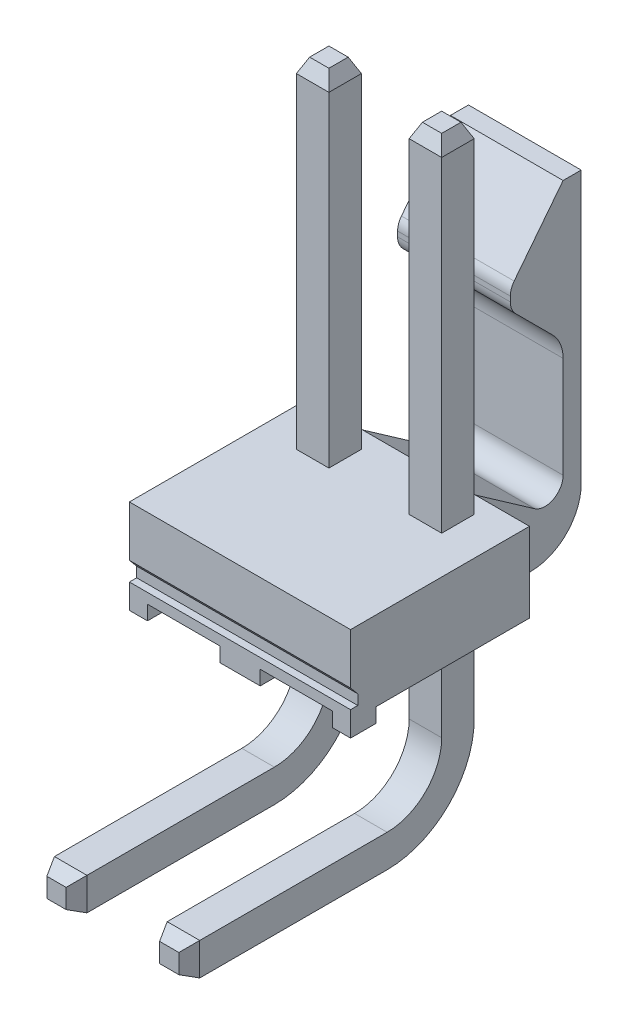
SolidWorks part; units mm, degrees
ref_plane "Front Plane" through (0, 0, 0) normal (0, 0, 1) x (1, 0, 0)
ref_plane "Top Plane" through (0, 0, 0) normal (0, 1, 0) x (1, 0, 0)
ref_plane "Right Plane" through (0, 0, 0) normal (1, 0, 0) x (0, 0, -1)
ref_plane "Plane2" through (1.98, 0, 0) normal (1, 0, 0) x (0, 0, -1)
ref_plane "Plane3" through (0, 12.83, 0) normal (0, 1, 0) x (1, 0, 0)
ref_plane "Plane4" through (0, 0, 7.11) normal (0, 0, 1) x (1, 0, 0)
sketch "Sketch17" plane through (0, 0, 0) normal (1, 0, 0) x (0, 0, -1)
  line L20 (-2.8893, -0.6837) -> (-2.8893, -1.0393)
  line L21 (-2.8893, -1.0393) -> (-3.1432, -1.0393)
  line L22 (-3.1432, -1.0393) -> (-3.1432, -1.905)
  line L23 (-3.1432, -1.905) -> (-2.2542, -1.905)
  line L24 (-2.2542, -1.905) -> (-2.2542, -1.397)
  line L25 (-2.2542, -1.397) -> (3.1432, -1.397)
  line L26 (3.1432, -1.397) -> (3.1432, 1.397) construction
  line L27 (3.1432, 1.397) -> (-3.1432, 1.397)
  line L28 (-3.1432, 1.397) -> (-3.1432, -0.381)
  line L29 (-3.1432, -0.381) -> (-2.8893, -0.6837)
  line L30 (3.1432, -1.905) -> (5.0863, -1.905) construction
  line L31 (6.8643, -0.127) -> (6.8644, 9.4234) construction
  line L32 (6.8644, 9.4234) -> (6.2294, 9.4234) construction
  line L33 (6.2294, 9.4234) -> (4.5098, 7.2224) construction
  line L34 (4.3751, 6.8315) -> (4.3751, 6.6552) construction
  line L35 (4.5611, 6.2062) -> (5.8574, 4.9099) construction
  line L36 (6.2294, 4.0119) -> (6.2294, 0.4559) construction
  line L37 (5.2301, -0.0642) -> (3.1432, 1.397) construction
  line L38 (3.1432, 1.397) -> (3.1432, -1.397)
  line L39 (3.1432, -1.397) -> (3.1432, -1.905) construction
  line L40 (-3.1432, -1000.381) -> (-3.1433, 48999.619) construction
  line L41 (0, -1000) -> (0, 49000) construction
  line L42 (3.1433, -1001.397) -> (3.1432, 48998.603) construction
  line L43 (6.2294, -999.5441) -> (6.2293, 49000.4559) construction
  line L44 (6.8644, -1000.127) -> (6.8643, 48999.873) construction
  line L45 (5.0102, -997.747) -> (5.0102, 49002.253) construction
  line L46 (-1000, 0) -> (49000, 0) construction
  line L47 (-996.8567, 1.397) -> (49003.1433, 1.397) construction
  line L48 (-996.8567, -1.397) -> (49003.1433, -1.397) construction
  line L49 (-996.8567, -1.905) -> (49003.1433, -1.905) construction
  line L50 (-993.7706, 9.4234) -> (49006.2294, 9.4234) construction
  arc A5 (5.0863, -1.905) -> (6.8643, -0.127) centre (5.0863, -0.127) ccw construction
  arc A6 (4.5098, 7.2224) -> (4.3751, 6.8315) centre (5.0101, 6.8315) ccw construction
  arc A7 (4.3751, 6.6552) -> (4.5611, 6.2062) centre (5.0101, 6.6552) ccw construction
  arc A8 (6.2294, 4.0119) -> (5.8574, 4.9099) centre (4.9594, 4.0119) ccw construction
  arc A9 (5.2301, -0.0642) -> (6.2294, 0.4559) centre (5.5943, 0.4559) ccw construction
  dimension "D15" = 1.778
  dimension "D22" = 0.635
  dimension "D26" = 0.635
  dimension "D27" = 0.635
  dimension "D32" = 1.27
  dimension "D1" = 1.397
  dimension "D2" = 1.397
  dimension "D3" = 6.2865
  dimension "D4" = 1.778
  dimension "D5" = 0.8657
  dimension "D6" = 0.508
  dimension "D7" = 0.889
  dimension "D8" = 3.1433
  dimension "D9" = 3.1432
  dimension "D10" = 40
  dimension "D11" = 2.2543
  dimension "D12" = 1.905
  dimension "D13" = 0.254
  dimension "D14" = 1.9431
  dimension "D16" = 1.778
  dimension "D17" = 3.0861
  dimension "D18" = 3.7211
  dimension "D19" = 2.4511
  dimension "D20" = 0.9411
  dimension "D21" = 35
  dimension "D23" = 9.4234
  dimension "D24" = 1.8542
  dimension "D25" = 0.1763
  dimension "D28" = 38
  dimension "D29" = 45
  dimension "D30" = 1.8161
  dimension "D31" = 5.4115
  dimension "D33" = 2.5919
  dimension "D34" = 0.635
extrude "Boss-Extrude14" add sketch "Sketch17" along normal blind 3.885 and the other way blind 3.885
sketch "Sketch18" plane through (0, 0, 0) normal (1, 0, 0) x (0, 0, -1)
  line L0 (6.2294, 9.4234) -> (4.5098, 7.2224) construction
  line L1 (6.8644, 9.4234) -> (6.2294, 9.4234) construction
  line L2 (6.8643, -0.127) -> (6.8644, 9.4234) construction
  line L3 (3.1432, -1.905) -> (5.0863, -1.905) construction
  line L5 (5.2301, -0.0642) -> (3.1432, 1.397) construction
  line L6 (4.5611, 6.2062) -> (5.8574, 4.9099) construction
  line L7 (6.2294, 4.0119) -> (6.2294, 0.4559) construction
  line L8 (4.3752, 6.8315) -> (4.3751, 6.6552) construction
  line L9 (6.2294, 9.4234) -> (4.5098, 7.2224)
  line L10 (6.8644, 9.4234) -> (6.2294, 9.4234)
  line L11 (6.8643, -0.127) -> (6.8644, 9.4234)
  line L12 (3.1432, -1.905) -> (5.0863, -1.905)
  line L13 (3.1432, 1.397) -> (3.1432, -1.905)
  line L14 (5.2301, -0.0642) -> (3.1432, 1.397)
  line L15 (4.5611, 6.2062) -> (5.8574, 4.9099)
  line L16 (6.2294, 4.0119) -> (6.2294, 0.4559)
  line L17 (4.3752, 6.8315) -> (4.3751, 6.6552)
  arc A0 (5.0863, -1.905) -> (6.8643, -0.127) centre (5.0863, -0.127) ccw construction
  arc A1 (5.2301, -0.0642) -> (6.2294, 0.4559) centre (5.5943, 0.4559) ccw construction
  arc A2 (6.2294, 4.0119) -> (5.8574, 4.9099) centre (4.9594, 4.0119) ccw construction
  arc A3 (4.3751, 6.6552) -> (4.5611, 6.2062) centre (5.0101, 6.6552) ccw construction
  arc A4 (4.5098, 7.2224) -> (4.3752, 6.8315) centre (5.0101, 6.8315) ccw construction
  arc A5 (5.0863, -1.905) -> (6.8643, -0.127) centre (5.0863, -0.127) ccw
  arc A6 (5.2301, -0.0642) -> (6.2294, 0.4559) centre (5.5943, 0.4559) ccw
  arc A7 (6.2294, 4.0119) -> (5.8574, 4.9099) centre (4.9594, 4.0119) ccw
  arc A8 (4.3751, 6.6552) -> (4.5611, 6.2062) centre (5.0101, 6.6552) ccw
  arc A9 (4.5098, 7.2224) -> (4.3752, 6.8315) centre (5.0101, 6.8315) ccw
extrude "Boss-Extrude15" add sketch "Sketch18" along normal blind 1.98 and the other way blind 1.98
sketch "Sketch19" plane through (0, 0, 2.2542) normal (0, 0, -1) x (-1, 0, 0)
  line L0 (0, -1000) -> (0, 49000) construction
  line L1 (3.885, -1.397) -> (-3.885, -1.397) construction
  line L2 (-3.25, -1.397) -> (-0.71, -1.397)
  line L3 (-3.25, -1.397) -> (-3.25, -1.905)
  line L4 (-3.25, -1.905) -> (-0.71, -1.905)
  line L5 (-0.71, -1.397) -> (-0.71, -1.905)
  line L6 (-3.25, -1.397) -> (-0.71, -1.905) construction
  line L7 (-3.25, -1.905) -> (-0.71, -1.397) construction
  line L8 (3.885, -1.905) -> (-3.885, -1.905) construction
  line L9 (3.25, -1.397) -> (0.71, -1.397)
  line L10 (0.71, -1.397) -> (0.71, -1.905)
  line L11 (3.25, -1.905) -> (0.71, -1.905)
  line L12 (3.25, -1.397) -> (3.25, -1.905)
  point P1 (-1.98, -1.651)
  dimension "D1" = 1.42
  dimension "D2" = 2.54
extrude "Cut-Extrude4" cut sketch "Sketch19" against normal through all
sketch "Sketch20" plane through (0, 12.83, 0) normal (0, 1, 0) x (1, 0, 0)
  line L8 (-1.4097, 1.3907) -> (-1.4097, 2.5337)
  line L9 (-1.4097, 2.5337) -> (-2.5527, 2.5337)
  line L10 (-2.5527, 2.5337) -> (-2.5527, 1.3907)
  line L11 (-2.5527, 1.3907) -> (-1.4097, 1.3907)
  line L12 (2.5527, 1.3907) -> (2.5527, 2.5337)
  line L13 (2.5527, 2.5337) -> (1.4097, 2.5337)
  line L14 (1.4097, 2.5337) -> (1.4097, 1.3907)
  line L15 (1.4097, 1.3907) -> (2.5527, 1.3907)
  line L16 (0, -1000) -> (0, 49000) construction
  point P9 (1.9812, 1.9622)
  point P12 (1.4097, 1.9622)
  point P13 (1.9812, 2.5337)
  dimension "D1" = 2.8194
  dimension "D2" = 2.8194
  dimension "D3" = 1.143
  dimension "D4" = 1.143
  dimension "D5" = 1.3907
  dimension "D6" = 1.143
extrude "Cut-Extrude5" cut sketch "Sketch20" against normal through all
sketch "Sketch22" plane through (0, 0, 7.11) normal (0, 0, 1) x (1, 0, 0)
  line L0 (-998.02, -7.3152) -> (49001.98, -7.3152) construction
  line L3 (1.9812, -987.17) -> (1.9812, 49012.83) construction
  point P3 (1.9812, -7.3152)
  dimension "D1" = 7.3152
sketch "Sketch21" plane through (1.98, 0, 0) normal (1, 0, 0) x (0, 0, -1)
  line L0 (1.9622, 12.83) -> (1.9622, -4.8275)
  line L1 (4.2748, 12.83) -> (-4.2748, 12.83) construction
  line L2 (-0.5255, -7.3152) -> (-7.11, -7.3152)
  line L3 (-7.11, 4.2748) -> (-7.11, -4.2748) construction
  line L4 (1.3922, 12.83) -> (1.3922, -4.8275) construction
  line L5 (-0.5255, -6.7452) -> (-7.11, -6.7452) construction
  line L6 (2.5322, 12.83) -> (2.5322, -4.8275) construction
  line L7 (-0.5255, -7.8852) -> (-7.11, -7.8852) construction
  arc A0 (1.9622, -4.8275) -> (-0.5255, -7.3152) centre (-0.5255, -4.8275) cw
  arc A1 (1.3922, -4.8275) -> (-0.5255, -6.7452) centre (-0.5255, -4.8275) cw construction
  arc A2 (2.5322, -4.8275) -> (-0.5255, -7.8852) centre (-0.5255, -4.8275) cw construction
  dimension "D1" = 0.57
  dimension "D3" = 1.9177
  dimension "D4" = 3.0577
  dimension "D2" = 0.57
sweep "Sweep1" add profiles "Sketch20<2>" path "Sketch21"
sketch "Sketch20<2>" plane through (0, 12.83, 0) normal (0, 1, 0) x (1, 0, 0) same geometry as "Sketch20"
sketch "Sketch23" plane through (0, 12.83, 0) normal (0, 1, 0) x (1, 0, 0)
  line L4 (1.4097, 1.3907) -> (2.5527, 1.3907)
  line L5 (2.5527, 1.3907) -> (2.5527, 2.5337)
  line L6 (2.5527, 2.5337) -> (1.4097, 2.5337)
  line L7 (1.4097, 2.5337) -> (1.4097, 1.3907)
  line L8 (1.4097, 1.3907) -> (2.5527, 1.3907)
  line L9 (2.5527, 1.3907) -> (2.5527, 2.5337)
  line L10 (2.5527, 2.5337) -> (1.4097, 2.5337)
  line L11 (1.4097, 2.5337) -> (1.4097, 1.3907)
  line L12 (-2.5527, 1.3907) -> (-1.4097, 1.3907)
  line L13 (-1.4097, 1.3907) -> (-1.4097, 2.5337)
  line L14 (-1.4097, 2.5337) -> (-2.5527, 2.5337)
  line L15 (-2.5527, 2.5337) -> (-2.5527, 1.3907)
  line L16 (-2.5527, 1.3907) -> (-1.4097, 1.3907)
  line L17 (-1.4097, 1.3907) -> (-1.4097, 2.5337)
  line L18 (-1.4097, 2.5337) -> (-2.5527, 2.5337)
  line L19 (-2.5527, 2.5337) -> (-2.5527, 1.3907)
  dimension "D1" = 0
  dimension "D2" = 0
extrude "Boss-Extrude16" add sketch "Sketch23" along normal blind 0.5 draft 25
sketch "Sketch24" plane through (0, 0, 7.11) normal (0, 0, 1) x (1, 0, 0)
  line L4 (2.5527, -6.7437) -> (1.4097, -6.7437)
  line L5 (1.4097, -6.7437) -> (1.4097, -7.8867)
  line L6 (1.4097, -7.8867) -> (2.5527, -7.8867)
  line L7 (2.5527, -7.8867) -> (2.5527, -6.7437)
  line L8 (2.5527, -6.7437) -> (1.4097, -6.7437)
  line L9 (1.4097, -6.7437) -> (1.4097, -7.8867)
  line L10 (1.4097, -7.8867) -> (2.5527, -7.8867)
  line L11 (2.5527, -7.8867) -> (2.5527, -6.7437)
  line L12 (-1.4097, -6.7437) -> (-2.5527, -6.7437)
  line L13 (-2.5527, -6.7437) -> (-2.5527, -7.8867)
  line L14 (-2.5527, -7.8867) -> (-1.4097, -7.8867)
  line L15 (-1.4097, -7.8867) -> (-1.4097, -6.7437)
  line L16 (-1.4097, -6.7437) -> (-2.5527, -6.7437)
  line L17 (-2.5527, -6.7437) -> (-2.5527, -7.8867)
  line L18 (-2.5527, -7.8867) -> (-1.4097, -7.8867)
  line L19 (-1.4097, -7.8867) -> (-1.4097, -6.7437)
  dimension "D1" = 0
  dimension "D2" = 0
extrude "Boss-Extrude17" add sketch "Sketch24" along normal blind 0.5 draft 25
other "Freeze***"
